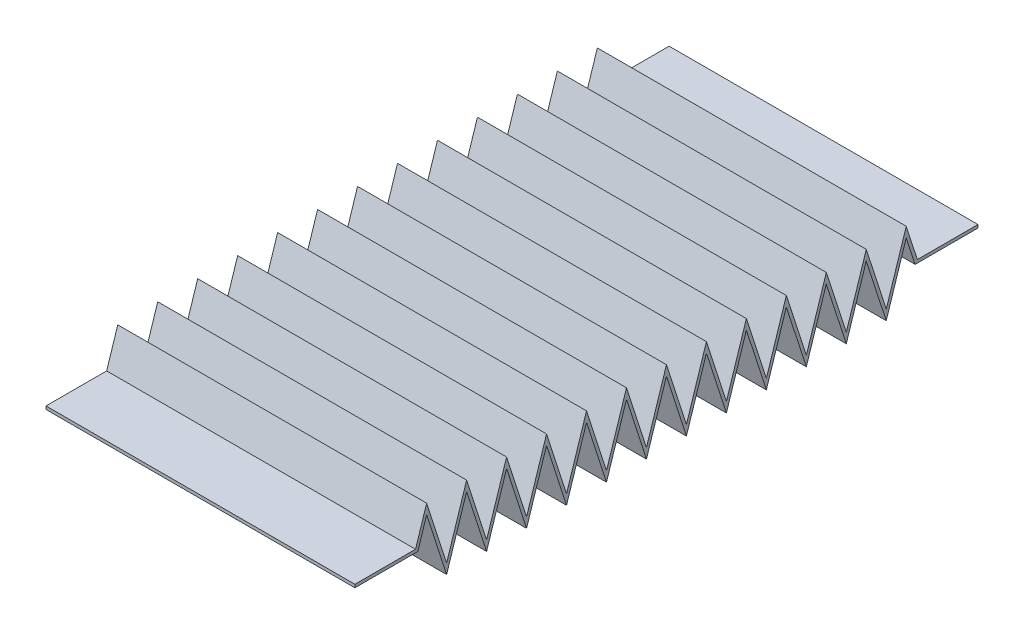
SolidWorks part; units mm, degrees
ref_plane "Front Plane" through (0, 0, 0) normal (0, 0, 1) x (1, 0, 0)
ref_plane "Top Plane" through (0, 0, 0) normal (0, 1, 0) x (1, 0, 0)
ref_plane "Right Plane" through (0, 0, 0) normal (1, 0, 0) x (0, 0, -1)
sketch "Sketch2" plane through (0, 0, 0) normal (0, 0, 1) x (1, 0, 0)
  line L1 (-27.5, 10) -> (27.5, 10)
  line L2 (-27.5, 10) -> (-27.5, 0)
  line L3 (-27.5, 0) -> (27.5, 0)
  line L4 (27.5, 10) -> (27.5, 0)
  point P4 (0, 0)
  dimension "D1" = 10
  dimension "D2" = 55
sketch "Sketch3" plane through (0, 0, 0) normal (1, 0, 0) x (0, 0, -1)
  line L0 (0, 10) -> (100.8682, 10) construction
  line L1 (0, 0) -> (100.8682, 0) construction
  line L3 (10, 5) -> (11.6174, 10)
  line L4 (11.6174, 10) -> (14.8521, 0)
  line L5 (14.8521, 0) -> (18.0868, 10)
  line L6 (18.0868, 10) -> (21.3216, 0)
  line L7 (21.3216, 0) -> (24.5563, 10)
  line L8 (24.5563, 10) -> (27.791, 0)
  line L9 (27.791, 0) -> (31.0257, 10)
  line L10 (31.0257, 10) -> (34.2605, 0)
  line L11 (34.2605, 0) -> (37.4952, 10)
  line L12 (37.4952, 10) -> (40.7299, 0)
  line L13 (40.7299, 0) -> (43.9647, 10)
  line L14 (43.9647, 10) -> (47.1994, 0)
  line L15 (47.1994, 0) -> (50.4341, 10)
  line L16 (50.4341, 10) -> (53.6688, 0)
  line L17 (53.6688, 0) -> (56.9036, 10)
  line L18 (56.9036, 10) -> (60.1383, 0)
  line L19 (0, 10) -> (0, 0) construction
  line L20 (60.1383, 0) -> (63.373, 10)
  line L21 (63.373, 10) -> (66.6078, 0)
  line L22 (66.6078, 0) -> (69.8425, 10)
  line L23 (69.8425, 10) -> (73.0772, 0)
  line L24 (73.0772, 0) -> (76.312, 10)
  line L25 (76.312, 10) -> (79.5467, 0)
  line L26 (79.5467, 0) -> (82.7814, 10)
  line L27 (82.7814, 10) -> (86.0161, 0)
  line L28 (86.0161, 0) -> (89.2509, 10)
  line L29 (89.2509, 10) -> (90.8682, 5)
  line L30 (100.8682, 10) -> (100.8682, 0) construction
  line L31 (10, 5) -> (0, 5)
  line L32 (90.8682, 5) -> (100.8682, 5)
  line L34 (100.8682, 22.75) -> (100.8682, 4.75) construction
  dimension "D2" = 10
  dimension "D1" = 10
  dimension "D3" = 10
extrude "Extrude-Thin1" add sketch "Sketch3" against normal mid plane 50 thin thin type mid plane wall 0.5
